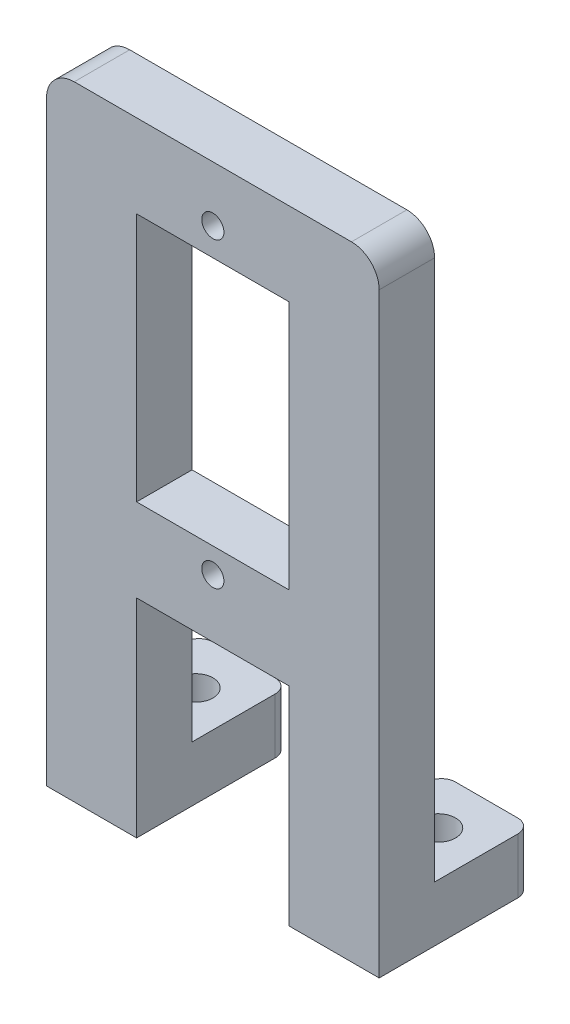
SolidWorks part; units mm, degrees
ref_plane "Front Plane" through (0, 0, 0) normal (0, 0, 1) x (1, 0, 0)
ref_plane "Top Plane" through (0, 0, 0) normal (0, 1, 0) x (1, 0, 0)
ref_plane "Right Plane" through (0, 0, 0) normal (1, 0, 0) x (0, 0, -1)
sketch "Sketch1" plane through (0, 0, 0) normal (0, 0, 1) x (1, 0, 0)
  line L0 (-15.24, -19.05) -> (-15.24, -38.1)
  line L1 (-6.985, 11.43) -> (6.985, 11.43)
  line L2 (-6.985, 11.43) -> (-6.985, -11.43)
  line L3 (-6.985, -11.43) -> (6.985, -11.43)
  line L4 (6.985, 11.43) -> (6.985, -11.43)
  line L5 (-15.24, 19.05) -> (15.24, 19.05)
  line L6 (-15.24, 19.05) -> (-15.24, -19.05)
  line L7 (-15.24, -19.05) -> (15.24, -19.05)
  line L8 (15.24, 19.05) -> (15.24, -19.05)
  line L9 (-15.24, -38.1) -> (-6.985, -38.1)
  line L10 (-6.985, -38.1) -> (-6.985, -19.05)
  line L11 (-15.24, -19.05) -> (-6.985, -19.05)
  line L12 (15.24, -19.05) -> (15.24, -38.1)
  line L13 (15.24, -38.1) -> (6.985, -38.1)
  line L14 (6.985, -38.1) -> (6.985, -19.05)
  line L15 (6.985, -19.05) -> (15.24, -19.05)
  point P5 (0, 11.43)
  point P6 (-6.985, 0)
  point P12 (0, 19.05)
  point P13 (-15.24, 0)
  dimension "D1" = 13.97
  dimension "D2" = 22.86
  dimension "D3" = 30.48
  dimension "D4" = 38.1
  dimension "D5" = 19.05
extrude "Boss-Extrude1" add sketch "Sketch1" along normal blind 5.08 contours L6 L5 L8 L7 | L11 L10 L9 L0 | L12 L13 L14 L15 | L2 L1 L4 L3
fillet "Fillet1" radius 2.54 2 edges at (15.24, 19.05, 2.54) (-15.24, 19.05, 2.54)
ref_plane "Plane1" through (0, -38.1, 0) normal (0, 1, 0) x (1, 0, 0)
sketch "Sketch3" plane through (0, -38.1, 0) normal (0, 1, 0) x (1, 0, 0)
  line L0 (-15.24, 0) -> (-15.24, 8.89)
  line L1 (-15.24, 8.89) -> (-6.985, 8.89)
  line L2 (-6.985, 8.89) -> (-6.985, 0)
  line L3 (-12.7, 0) -> (12.7, 0) construction
  line L4 (-6.985, 0) -> (-15.24, 0)
  line L5 (-15.24, 0) -> (-6.985, 0) construction
  dimension "D2" = 8.89
extrude "Boss-Extrude2" add sketch "Sketch3" along normal blind 5.08
sketch "Sketch5" plane through (0, 0, 5.08) normal (0, 0, 1) x (1, 0, 0)
  line L2 (-6.985, 11.43) -> (6.985, 11.43) construction
  circle A0 centre (0, 13.97) radius 1.016
  circle A1 centre (0, -13.716) radius 1.016
  dimension "D1" = 2.032
  dimension "D2" = 2.032
  dimension "D3" = 27.686
  dimension "D4" = 2.54
extrude "Cut-Extrude1" cut sketch "Sketch5" against normal blind 5.08
sketch "Sketch6" plane through (0, -33.02, 0) normal (0, 1, 0) x (1, 0, 0)
  line L0 (-15.24, 8.89) -> (-15.24, 0) construction
  line L1 (-6.985, 8.89) -> (-15.24, 8.89) construction
  circle A0 centre (-11.1125, 4.445) radius 1.6
  point P4 (-15.24, 4.445)
  point P7 (-11.1125, 8.89)
  dimension "D1" = 3.2
extrude "Cut-Extrude2" cut sketch "Sketch6" against normal blind 5.08
mirror "Mirror2" about plane through (0, 0, 0) normal (1, 0, 0) of "Cut-Extrude2", "Boss-Extrude2"
fillet "Fillet2" radius 1.27 4 edges at (-6.985, -35.56, -8.89) (15.24, -35.56, -8.89) (6.985, -35.56, -8.89) (-15.24, -35.56, -8.89)
